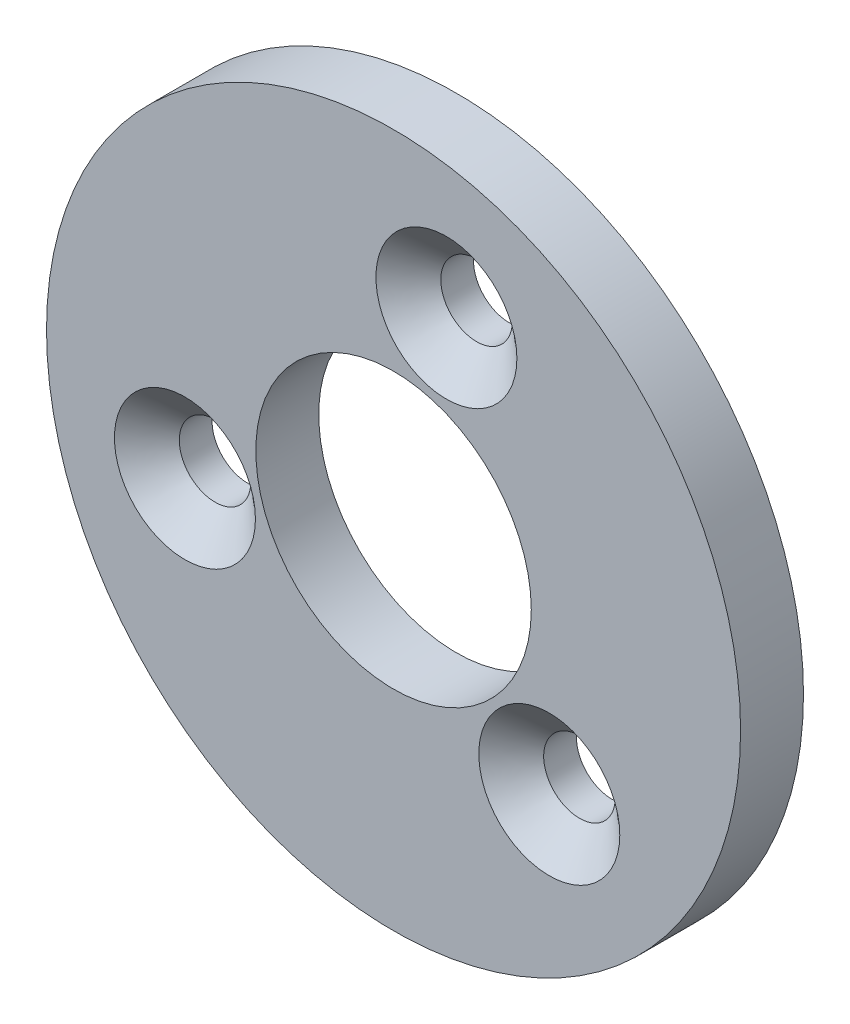
SolidWorks part; units mm, degrees
ref_plane "Front Plane" through (0, 0, 0) normal (0, 0, 1) x (1, 0, 0)
ref_plane "Top Plane" through (0, 0, 0) normal (0, 1, 0) x (1, 0, 0)
ref_plane "Right Plane" through (0, 0, 0) normal (1, 0, 0) x (0, 0, -1)
sketch "Sketch1" plane through (0, 0, 0) normal (0, 0, 1) x (1, 0, 0)
  circle A0 centre (0, 0) radius 16
  dimension "D1" = 32
extrude "Boss-Extrude1" add sketch "Sketch1" along normal blind 2.9
sketch "Sketch2" plane through (0, 0, 2.9) normal (0, 0, 1) x (1, 0, 0)
  circle A3 centre (-9.6176, -2.7388) radius 1.65
  circle A4 centre (-9.6176, -2.7388) radius 1.65
  circle A5 centre (7.1807, -6.9597) radius 1.65
  circle A6 centre (7.1807, -6.9597) radius 1.65
  circle A7 centre (2.437, 9.6985) radius 1.65
  circle A8 centre (2.437, 9.6985) radius 1.65
  dimension "D2" = 0
  dimension "D3" = 0
  dimension "D4" = 0
extrude "Cut-Extrude1" cut sketch "Sketch2" against normal through all
chamfer "Chamfer1" distance 1.6 angle 41 3 edges at (-7.9676, -2.7388, 2.9) (4.087, 9.6985, 2.9) (8.8307, -6.9597, 2.9) first distance on face at (8.8307, -6.9597, 2.9)
sketch "Sketch3" plane through (0, 0, 2.9) normal (0, 0, 1) x (1, 0, 0)
  circle A1 centre (0, 0) radius 6.35
  circle A2 centre (0, 0) radius 6.35
  dimension "D1" = 0
extrude "Cut-Extrude2" cut sketch "Sketch3" against normal through all
equation "\"smallPulleyTeeth\"= 15"
equation "\"largePulleyTeeth\"= 30"
equation "\"eighthThick\"= 2.9mm"
equation "\"sixteenthThick\" = 1.7mm"
equation "\"quarterThick\"=5.9mm"
equation "\"OD\" = 145mm"
equation "\"puckAngle\" = 60.5deg"
equation "\"puckDiam\" = 76.5mm"
equation "\"axlePress\" = 5.9mm"
equation "\"press\" = 0.2mm"
equation "\"wheelClear\" = 0.3mm"
equation "\"10-32clear\" = 4.5mm"
equation "\"D1@Boss-Extrude1\"=\"eighthThick\""
equation "\"D1@Chamfer1\"=(6.5-\"6-32clear\")/2"
equation "\"6-32clear\" = 3.3mm"
equation "\"8-32clear\" = 4.0mm"
